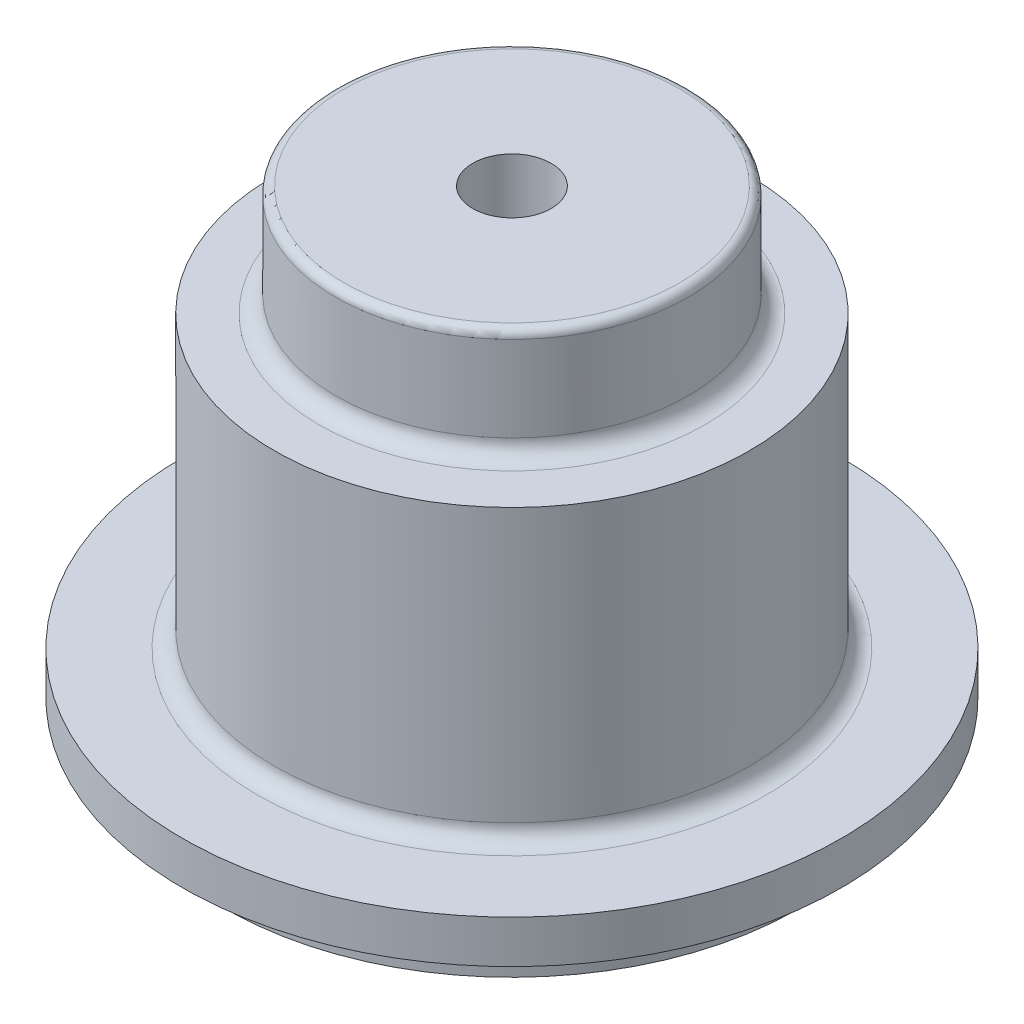
SolidWorks part; units mm, degrees
ref_plane "Front Plane" through (0, 0, 0) normal (0, 0, 1) x (1, 0, 0)
ref_plane "Top Plane" through (0, 0, 0) normal (0, 1, 0) x (1, 0, 0)
ref_plane "Right Plane" through (0, 0, 0) normal (1, 0, 0) x (0, 0, -1)
sketch "Sketch1" plane through (0, 0, 0) normal (0, 0, 1) x (1, 0, 0)
  line L0 (0, 0) -> (0, 49.2)
  line L1 (12.3346, 0) -> (21.75, 0)
  line L2 (21.75, 0) -> (21.75, 3)
  line L3 (21.75, 3) -> (25, 3)
  line L4 (25, 3) -> (25, 6.25)
  line L5 (25, 6.25) -> (18.0356, 6.25)
  line L6 (2.9747, 28.2359) -> (2.9747, 36.6111)
  line L9 (2.9747, 36.6111) -> (13.3704, 36.6111)
  line L10 (12.3346, 0) -> (12.3346, 25.3)
  line L11 (12.3346, 25.3) -> (2.9747, 25.3)
  line L12 (18.0356, 6.25) -> (18.0356, 28.2359)
  line L13 (18.0356, 28.2359) -> (13.3704, 28.2359)
  line L14 (13.3704, 28.2359) -> (13.3704, 36.6111)
  line L15 (2.9747, 28.2359) -> (0, 28.2359)
  line L16 (0, 28.2359) -> (0, 25.3)
  line L17 (0, 25.3) -> (2.8306, 25.3)
  line L18 (2.9747, 25.3) -> (2.8306, 25.3)
  dimension "D1" = 49.2
  dimension "D5" = 25.3
  dimension "D6" = 21.75
  dimension "D7" = 25
  dimension "D8" = 3
  dimension "D9" = 3.25
revolve "Revolve4" add sketch "Sketch1" angle 360 about L0 region at (12.8541, 19.4521, 0)
fillet "Fillet2" radius 1.27 2 edges at (0, 6.25, -18.0356) (0, 28.2359, -13.3704)
fillet "Fillet3" radius 0.635 1 edges at (0, 36.6111, -13.3704)
equation "\"`1mm\"=10"
